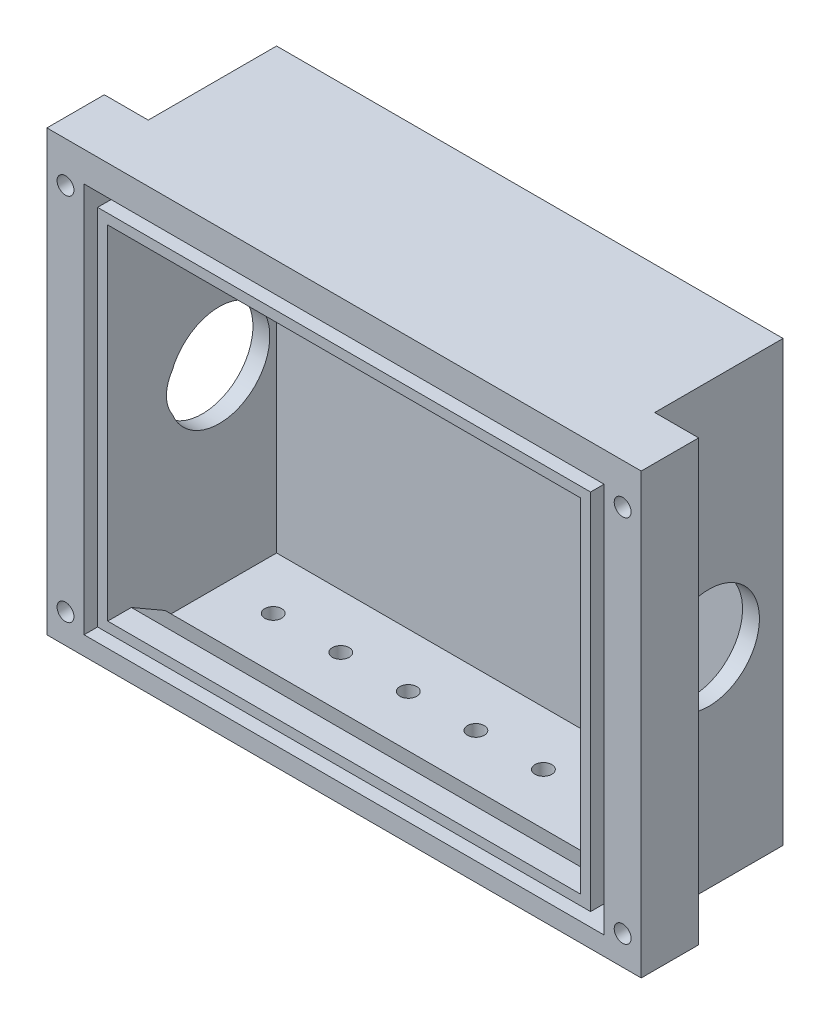
SolidWorks part; units mm, degrees
ref_plane "Front Plane" through (0, 0, 0) normal (0, 0, 1) x (1, 0, 0)
ref_plane "Top Plane" through (0, 0, 0) normal (0, 1, 0) x (1, 0, 0)
ref_plane "Right Plane" through (0, 0, 0) normal (1, 0, 0) x (0, 0, -1)
sketch "Sketch1" plane through (0, 0, 0) normal (0, 1, 0) x (1, 0, 0)
  circle A0 centre (0, 0) radius 172.5
  dimension "D1" = 345
extrude "Boss-Extrude1" add sketch "Sketch1" along normal blind 10
sketch "Sketch2" plane through (0, 10, 0) normal (0, 1, 0) x (1, 0, 0)
  circle A0 centre (-75.91, -178.72) radius 48.41
  circle A1 centre (75.91, -178.72) radius 48.41
  dimension "D1" = 96.82
  dimension "D2" = 96.82
  dimension "D3" = 151.82
  dimension "D4" = 0
  dimension "D5" = 178.72
  dimension "D6" = 75.91
extrude "Cut-Extrude1" cut sketch "Sketch2" against normal blind 10
sketch "Sketch3" plane through (0, 10, 0) normal (0, 1, 0) x (1, 0, 0)
  line L0 (-75.91, -178.72) -> (75.91, -178.72)
  line L1 (-98.9683, -119.81) -> (98.9683, -119.81)
  line L2 (0, -178.72) -> (0, -205.4095)
  line L3 (0, -116.81) -> (0, -103.1109)
  line L4 (-97.8835, -116.81) -> (97.8835, -116.81)
  arc A0 (97.8835, -116.81) -> (-97.8835, -116.81) centre (0, 0) ccw
  arc A1 (98.9683, -119.81) -> (-98.9683, -119.81) centre (0, 0) ccw
  dimension "D1" = 304.8
  dimension "D2" = 3
  dimension "D4" = 0
extrude "Boss-Extrude2" add sketch "Sketch3" along normal blind 5 contours L1 A1 A0 L4 region at (0, 10, -154.9849)
sketch "Sketch4" plane through (0, 10, 0) normal (0, 1, 0) x (1, 0, 0)
  line L0 (-28.2612, -170.1692) -> (28.2612, -170.1692)
  line L1 (28.2612, -170.1692) -> (28.2612, -183.8361)
  line L2 (28.2612, -183.8361) -> (-30.3005, -183.8361)
  line L3 (-30.3005, -183.8361) -> (-28.2612, -170.1692)
extrude "Cut-Extrude2" cut sketch "Sketch4" against normal blind 497
sketch "Sketch5" plane through (0, 10, 0) normal (0, 1, 0) x (1, 0, 0)
  line L0 (-166.525, 159.566) -> (-166.525, -120.1627)
  line L1 (166.525, 178.4393) -> (166.525, -124.881)
  line L2 (-148.2899, 170.4208) -> (120.6541, 170.4208)
  line L3 (28.2612, -170.1692) -> (-28.2612, -170.1692) construction
  line L5 (-166.525, 170.4208) -> (166.525, 170.4208)
  line L6 (-166.525, 170.4208) -> (-166.525, -186.2191)
  line L7 (-166.525, -186.2191) -> (166.525, -186.2191)
  line L8 (166.525, 170.4208) -> (166.525, -186.2191)
  line L9 (-215.4787, 226.3504) -> (214.5081, 226.3504)
  line L10 (-215.4787, 226.3504) -> (-215.4787, -259.9327)
  line L11 (-215.4787, -259.9327) -> (214.5081, -259.9327)
  line L12 (214.5081, 226.3504) -> (214.5081, -259.9327)
  arc M6 (102.8405, -138.4922) -> (-102.8405, -138.4922) centre (0, 0) ccw
  dimension "D1" = 333.05
  dimension "D2" = 166.525
  dimension "D3" = 340.59
extrude "Cut-Extrude6" cut sketch "Sketch5" against normal blind 497 contours L2 M6 | L1 M6 | L0 M6 region at (-168.9186, 10, 0) region at (0, 10, -171.2529) region at (168.9186, 10, 0)
sketch "Sketch6" plane through (0, 10, 0) normal (0, 1, 0) x (1, 0, 0)
  line L0 (-97.8835, -116.81) -> (97.8835, -116.81)
  line L1 (-97.8835, -116.81) -> (-97.8835, -61.81)
  line L2 (97.8835, -116.81) -> (97.8835, -61.81)
  line L3 (97.8835, -61.81) -> (-97.8835, -61.81)
  line L4 (92.8835, -66.81) -> (-92.8835, -66.81)
  line L5 (-92.8835, -111.81) -> (-92.8835, -66.81)
  line L6 (-92.8835, -111.81) -> (92.8835, -111.81)
  line L7 (92.8835, -111.81) -> (92.8835, -66.81)
  dimension "D1" = 55
  dimension "D2" = 5
extrude "Boss-Extrude3" add sketch "Sketch6" along normal blind 133.35
sketch "Sketch7" plane through (0, 10, 0) normal (0, 1, 0) x (1, 0, 0)
  line L1 (-92.8835, -66.81) -> (92.8835, -66.81)
  line L2 (-92.8835, -66.81) -> (-92.8835, -111.81)
  line L3 (-92.8835, -111.81) -> (92.8835, -111.81)
  line L4 (92.8835, -66.81) -> (92.8835, -111.81)
extrude "Boss-Extrude4" add sketch "Sketch7" along normal blind 5
sketch "Sketch8" plane through (0, 10, 0) normal (0, 1, 0) x (1, 0, 0)
  line L0 (-112.8835, -61.81) -> (-112.8835, -101.2671)
  line L1 (-97.8835, -61.81) -> (97.8835, -61.81)
  line L2 (-97.8835, -61.81) -> (-97.8835, -115.8298)
  line L4 (97.8835, -61.81) -> (97.8835, -115.8298)
  line L6 (112.8835, -46.81) -> (112.8835, -101.2671)
  line L7 (-88.0285, -46.81) -> (112.8835, -46.81)
  line L8 (-112.8835, -46.81) -> (-112.8835, -131.81) construction
  line L9 (-112.8835, -131.81) -> (112.8835, -131.81) construction
  line L10 (112.8835, -46.81) -> (112.8835, -131.81) construction
  line L11 (74.9923, -131.81) -> (76.4976, -131.81)
  line L12 (-97.8835, -116.81) -> (97.8835, -116.81) construction
  line L13 (97.8835, -61.81) -> (97.8835, -116.81) construction
  line L14 (-97.8835, -61.81) -> (-97.8835, -116.81) construction
  line L15 (-112.8835, -46.81) -> (112.8835, -46.81) construction
  line L18 (-112.8835, -61.81) -> (-88.0285, -61.81)
  line L19 (-88.0285, -46.81) -> (-88.0285, -61.81)
  arc A1 (-112.8835, -101.2671) -> (-96.7117, -116.81) centre (0, 0) ccw
  arc A5 (97.8835, -115.8298) -> (112.8835, -101.2671) centre (0, 0) ccw
  line M3 (-97.8835, -116.81) -> (-97.8835, -61.81)
  line M5 (97.8835, -61.81) -> (97.8835, -116.81)
  dimension "D1" = 15
extrude "Boss-Extrude5" add sketch "Sketch8" along normal blind 8 contours L0 A1 L18 M3 | A5 L6 L7 L19 L1 M5 region at (-104.9975, 10, 85.5341) region at (29.9995, 10, 60.2371)
chamfer "Chamfer1" distance 8 angle 38 3 edges at (-97.8835, 18, 88.8199) (4.9275, 18, 61.81) (97.8835, 18, 88.8199) first distance on face at (-97.8835, 51.1, 100.8157) first distance on face at (-50.228, 47.3375, 61.81) first distance on face at (97.8835, 51.1, 100.8157)
fillet "Fillet1" radius 38 3 edges at (-97.8835, 26, 88.8199) (4.9275, 26, 61.81) (97.8835, 26, 88.8199)
sketch "Sketch9" plane through (0, 10, 0) normal (0, 1, 0) x (1, 0, 0)
  circle A0 centre (0, 0) radius 374.0793
extrude "Cut-Extrude7" cut sketch "Sketch9" against normal blind 93
sketch "Sketch10" plane through (0, 10, 0) normal (0, -1, 0) x (1, 0, 0)
  circle A0 centre (0, 0) radius 152.4
  circle A1 centre (0, 0) radius 229.3861
extrude "Cut-Extrude8" cut sketch "Sketch10" against normal blind 93 and the other way blind 93
sketch "Sketch11" plane through (0, 143.35, 0) normal (0, 1, 0) x (1, 0, 0)
  line L0 (47.0835, -61.81) -> (47.0835, -116.81)
  line L1 (97.8835, -61.81) -> (-97.8835, -61.81) construction
  line L2 (-97.8835, -116.81) -> (97.8835, -116.81) construction
  line L3 (97.8835, -116.81) -> (97.8835, -61.81) construction
  line L4 (47.0835, -61.81) -> (-97.8835, -61.81)
  line L5 (-97.8835, -61.81) -> (-97.8835, -116.81)
  line L6 (-97.8835, -116.81) -> (47.0835, -116.81)
  line L8 (-140.8808, -21.3721) -> (150.5625, -21.3721)
  line L9 (-140.8808, -21.3721) -> (-140.8808, -156.1708)
  line L10 (-140.8808, -156.1708) -> (150.5625, -156.1708)
  line L11 (150.5625, -21.3721) -> (150.5625, -156.1708)
  dimension "D1" = 50.8
extrude "Cut-Extrude9" cut sketch "Sketch11" against normal blind 143
sketch "Sketch12" plane through (0, 143.35, 0) normal (0, 1, 0) x (1, 0, 0)
  line L1 (47.0835, -61.81) -> (52.0835, -61.81)
  line L2 (47.0835, -61.81) -> (47.0835, -116.81)
  line L3 (47.0835, -116.81) -> (52.0835, -116.81)
  line L4 (52.0835, -61.81) -> (52.0835, -116.81)
  dimension "D1" = 5
extrude "Boss-Extrude6" add sketch "Sketch12" against normal up to surface (133.35 mm away) up to face at (-25.4, 10, 89.31)
sketch "Sketch13" plane through (-97.8835, 0, 0) normal (-1, 0, 0) x (0, 0, 1)
  line L0 (61.81, 10) -> (116.81, 10) construction
  circle A0 centre (89.4188, 75) radius 10
  dimension "D1" = 20
  dimension "D2" = 65
extrude "Cut-Extrude10" cut sketch "Sketch13" against normal blind 58
sketch "Sketch14" plane through (0, 143.35, 0) normal (0, 1, 0) x (1, 0, 0)
  line L1 (-92.8835, -66.81) -> (47.0835, -66.81)
  line L2 (-92.8835, -66.81) -> (-92.8835, -111.81)
  line L3 (-92.8835, -111.81) -> (47.0835, -111.81)
  line L4 (47.0835, -66.81) -> (47.0835, -111.81)
extrude "Boss-Extrude7" add sketch "Sketch14" against normal blind 5
sketch "Sketch15" plane through (0, 0, 116.81) normal (0, 0, 1) x (1, 0, 0)
  line L1 (-92.8835, 138.35) -> (47.0835, 138.35)
  line L2 (-92.8835, 138.35) -> (-92.8835, 15)
  line L3 (-92.8835, 15) -> (47.0835, 15)
  line L4 (47.0835, 138.35) -> (47.0835, 15)
extrude "Cut-Extrude11" cut sketch "Sketch15" against normal blind 13
sketch "Sketch16" plane through (0, 0, 116.81) normal (0, 0, 1) x (1, 0, 0)
  line L0 (-107.8835, 143.35) -> (-107.8835, 10)
  line L1 (-92.8835, 138.35) -> (47.0835, 138.35)
  line L2 (-92.8835, 138.35) -> (-92.8835, 15)
  line L3 (-92.8835, 15) -> (47.0835, 15)
  line L4 (47.0835, 138.35) -> (47.0835, 15)
  line L6 (62.0835, 143.35) -> (62.0835, 10)
  line L8 (-107.8835, 143.35) -> (62.0835, 143.35)
  line L9 (-107.8835, 10) -> (62.0835, 10)
  line L10 (-107.8835, 153.35) -> (-107.8835, 0) construction
  line L11 (-107.8835, 0) -> (62.0835, 0) construction
  line L12 (62.0835, 153.35) -> (62.0835, 0) construction
  line L13 (-107.8835, 153.35) -> (62.0835, 153.35) construction
  line L14 (-92.8835, 76.675) -> (47.0835, 76.675)
  line L15 (-92.8835, 127.475) -> (47.0835, 127.475)
  line L16 (-92.8835, 127.475) -> (-92.8835, 25.875)
  line L17 (-92.8835, 25.875) -> (47.0835, 25.875)
  line L18 (47.0835, 127.475) -> (47.0835, 25.875)
  line L19 (-22.9, 127.475) -> (-22.9, 25.875)
  point P22 (-92.8835, 76.675)
  point P25 (-22.9, 138.35)
  line M11 (47.0835, 15) -> (-92.8835, 15)
  line M12 (-92.8835, 15) -> (-92.8835, 138.35)
  line M13 (-92.8835, 138.35) -> (47.0835, 138.35)
  line M14 (47.0835, 138.35) -> (47.0835, 15)
  line M15 (-97.8835, 10) -> (52.0835, 10)
  line M16 (52.0835, 10) -> (52.0835, 143.35)
  line M17 (52.0835, 143.35) -> (-97.8835, 143.35)
  line M18 (-97.8835, 143.35) -> (-97.8835, 10)
  dimension "D2" = 101.6
  dimension "D3" = 0
  dimension "D4" = 0
  dimension "D5" = 0
  dimension "D1" = 15
extrude "Boss-Extrude9" add sketch "Sketch16" against normal blind 17 contours L0 L9 L8 M18 | L4 L2 M18 M15 M16 M17 M14 M11 M12 M13 | L9 L6 L8 M16 | L15 M12 M14 M13 | L17 M12 M11 M14 region at (-102.8835, 76.675, 116.81) region at (-22.9, 141.3432, 116.81) region at (57.0835, 76.675, 116.81) region at (-22.9, 132.9125, 116.81) region at (-22.9, 20.4375, 116.81)
sketch "Sketch17" plane through (0, 0, 116.81) normal (0, 0, 1) x (1, 0, 0)
  line L0 (-95.8835, 130.475) -> (-95.8835, 22.875)
  line L1 (-92.8835, 127.475) -> (47.0835, 127.475)
  line L2 (-92.8835, 127.475) -> (-92.8835, 25.875)
  line L3 (-92.8835, 25.875) -> (47.0835, 25.875)
  line L4 (47.0835, 127.475) -> (47.0835, 25.875)
  line L5 (-95.8835, 22.875) -> (50.0835, 22.875)
  line L6 (50.0835, 130.475) -> (50.0835, 22.875)
  line L7 (-95.8835, 130.475) -> (50.0835, 130.475)
  line L8 (-99.8835, 134.475) -> (54.0835, 134.475)
  line L9 (54.0835, 134.475) -> (54.0835, 18.875)
  line L10 (-99.8835, 18.875) -> (54.0835, 18.875)
  line L11 (-99.8835, 134.475) -> (-99.8835, 18.875)
  dimension "D1" = 3
  dimension "D2" = 4
extrude "Cut-Extrude12" cut sketch "Sketch17" against normal blind 10 contours L8 L11 L10 L9 L0 L7 L6 L5 region at (-22.9, 132.5497, 116.81)
sketch "Sketch20" plane through (0, 0, 116.81) normal (0, 0, 1) x (1, 0, 0)
  line L0 (-107.8835, 143.35) -> (-107.8835, 10) construction
  line L1 (-110.8835, 146.35) -> (65.0835, 146.35)
  line L2 (-110.8835, 146.35) -> (-110.8835, 7)
  line L3 (-110.8835, 7) -> (65.0835, 7)
  line L4 (65.0835, 146.35) -> (65.0835, 7)
  line L5 (62.0835, 143.35) -> (62.0835, 10) construction
  line L6 (-107.8835, 10) -> (62.0835, 10) construction
  line L7 (-107.8835, 143.35) -> (62.0835, 143.35) construction
  line L9 (-107.8835, 143.35) -> (62.0835, 143.35)
  line L10 (-107.8835, 143.35) -> (-107.8835, 10)
  line L11 (-107.8835, 10) -> (62.0835, 10)
  line L12 (62.0835, 143.35) -> (62.0835, 10)
  line L13 (-110.8835, 7) -> (65.0835, 7)
  line L14 (-110.8835, 7) -> (-110.8835, 13.35)
  line L15 (-110.8835, 13.35) -> (65.0835, 13.35)
  line L16 (65.0835, 7) -> (65.0835, 13.35)
  line M13 (-107.8835, 10) -> (62.0835, 10)
  line M14 (62.0835, 10) -> (62.0835, 143.35)
  dimension "D1" = 3
  dimension "D2" = 3
  dimension "D3" = 3
  dimension "D4" = 3
  dimension "D5" = 6.35
chamfer "Chamfer2" distance 10 angle 30 2 edges at (-22.9, 25.875, 99.81) (-22.9, 127.475, 99.81) first distance on face at (-22.9, 25.875, 108.31) first distance on face at (-22.9, 132.9125, 99.81)
sketch "Sketch24" plane through (-97.8835, 0, 0) normal (-1, 0, 0) x (0, 0, 1)
  line L0 (99.81, 143.35) -> (99.81, 10) construction
  circle A1 centre (83.81, 75) radius 15
  dimension "D1" = 30
  dimension "D2" = 16
extrude "Cut-Extrude16" cut sketch "Sketch24" against normal blind 177.5
extrude "Cut-Extrude17" cut sketch "Sketch20" against normal blind 177.5 contours L15 L2 L3 L4 L10 M14 M13 | L15 L10 M13 M14 region at (-22.9, 8.6165, 116.81) region at (-22.9, 11.675, 116.81)
sketch "Sketch25" plane through (0, 13.35, 0) normal (0, -1, 0) x (-1, 0, 0)
  line L1 (-47.0835, -66.81) -> (92.8835, -66.81)
  line L2 (-47.0835, -66.81) -> (-47.0835, -105.5835)
  line L3 (-47.0835, -105.5835) -> (92.8835, -105.5835)
  line L4 (92.8835, -66.81) -> (92.8835, -105.5835)
extrude "Boss-Extrude11" add sketch "Sketch25" against normal blind 5
sketch "Sketch26" plane through (0, 0, 116.81) normal (0, 0, 1) x (1, 0, 0)
  line L0 (-107.8835, 143.35) -> (-107.8835, 13.35) construction
  line L1 (-110.8835, 143.35) -> (-107.8835, 143.35)
  line L2 (-110.8835, 143.35) -> (-110.8835, 13.35)
  line L3 (-110.8835, 13.35) -> (-107.8835, 13.35)
  line L4 (65.0835, 143.35) -> (65.0835, 13.35)
  line L5 (62.0835, 143.35) -> (62.0835, 13.35) construction
  line L6 (62.0835, 13.35) -> (65.0835, 13.35)
  line L8 (-107.8835, 143.35) -> (-107.8835, 13.35)
  line L10 (62.0835, 143.35) -> (62.0835, 13.35)
  line L11 (62.0835, 143.35) -> (65.0835, 143.35)
  dimension "D1" = 3
  dimension "D2" = 3
extrude "Boss-Extrude12" add sketch "Sketch26" against normal up to surface (17 mm away) up to face at (57.0835, 78.35, 99.81)
sketch "Sketch18" plane through (0, 0, 116.81) normal (0, 0, 1) x (1, 0, 0)
  line L7 (-99.8835, 134.475) -> (-99.8835, 18.875) construction
  line L8 (54.0835, 134.475) -> (54.0835, 18.875) construction
  circle A2 centre (-105.3835, 22) radius 2.5
  circle A3 centre (59.5835, 22) radius 2.5
  circle A4 centre (59.5835, 131.35) radius 2.5
  circle A5 centre (-105.3835, 131.35) radius 2.5
  point P10 (-22.9, 76.675)
  dimension "D4" = 5
  dimension "D5" = 5
  dimension "D10" = 5.5
  dimension "D12" = 5.5
extrude "Cut-Extrude19" cut sketch "Sketch18" against normal blind 26
sketch "Sketch27" plane through (0, 0, 66.81) normal (0, 0, 1) x (1, 0, 0)
  line L0 (47.0835, 138.35) -> (-92.8835, 138.35) construction
  line L1 (-12.9165, 133.35) -> (35.0835, 133.35)
  line L2 (-12.9165, 133.35) -> (-12.9165, 128.35)
  line L3 (-12.9165, 128.35) -> (35.0835, 128.35)
  line L4 (35.0835, 133.35) -> (35.0835, 128.35)
  line L5 (47.0835, 18.35) -> (47.0835, 138.35) construction
  dimension "D1" = 48
  dimension "D2" = 5
  dimension "D3" = 60
  dimension "D4" = 5
extrude "Cut-Extrude20" cut sketch "Sketch27" against normal blind 23
sketch "Sketch28" plane through (0, 18.35, 0) normal (0, 1, 0) x (1, 0, 0)
  line L0 (-92.8835, -99.81) -> (-92.8835, -66.81) construction
  line L1 (-92.8835, -66.81) -> (47.0835, -66.81) construction
  circle A0 centre (-77.8835, -82.81) radius 2.5
  circle A1 centre (-57.8835, -82.81) radius 2.5
  circle A2 centre (-37.8835, -82.81) radius 2.5
  circle A3 centre (-17.8835, -82.81) radius 2.5
  circle A4 centre (2.1165, -82.81) radius 2.5
  circle A5 centre (22.1165, -82.81) radius 2.5
  dimension "D1" = 5
  dimension "D2" = 15
  dimension "D3" = 16
  dimension "D4" = 6
extrude "Cut-Extrude21" cut sketch "Sketch28" against normal blind 10
sketch "Sketch29" plane through (0, 0, 61.81) normal (0, 0, -1) x (-1, 0, 0)
  line L0 (97.8835, 13.35) -> (-52.0835, 13.35) construction
  line L1 (39.6909, 98.35) -> (54.6909, 98.35)
  line L2 (39.6909, 98.35) -> (39.6909, 68.35)
  line L3 (39.6909, 68.35) -> (54.6909, 68.35)
  line L4 (54.6909, 98.35) -> (54.6909, 68.35)
  dimension "D1" = 30
  dimension "D2" = 15
  dimension "D3" = 55
extrude "Boss-Extrude13" add sketch "Sketch29" along normal blind 10
sketch "Sketch30" plane through (-54.6909, 0, 0) normal (-1, 0, 0) x (0, 0, 1)
  line L0 (51.81, 68.35) -> (61.81, 68.35) construction
  line L1 (61.81, 98.35) -> (57.81, 98.35)
  line L2 (61.81, 98.35) -> (61.81, 68.35)
  line L3 (61.81, 68.35) -> (57.81, 68.35)
  line L4 (57.81, 98.35) -> (57.81, 68.35)
  line L5 (57.81, 94.85) -> (61.81, 94.85)
  line L6 (57.81, 71.85) -> (61.81, 71.85)
  point P11 (59.81, 98.35)
  dimension "D1" = 4
  dimension "D2" = 3.5
  dimension "D3" = 3.5
extrude "Cut-Extrude22" cut sketch "Sketch30" against normal blind 21 contours L4 L6 L2 L5 region at (-54.6909, 83.35, 59.81)
chamfer "Chamfer3" distance 6 angle 45 2 edges at (-47.1909, 68.35, 61.81) (-47.1909, 98.35, 61.81)
